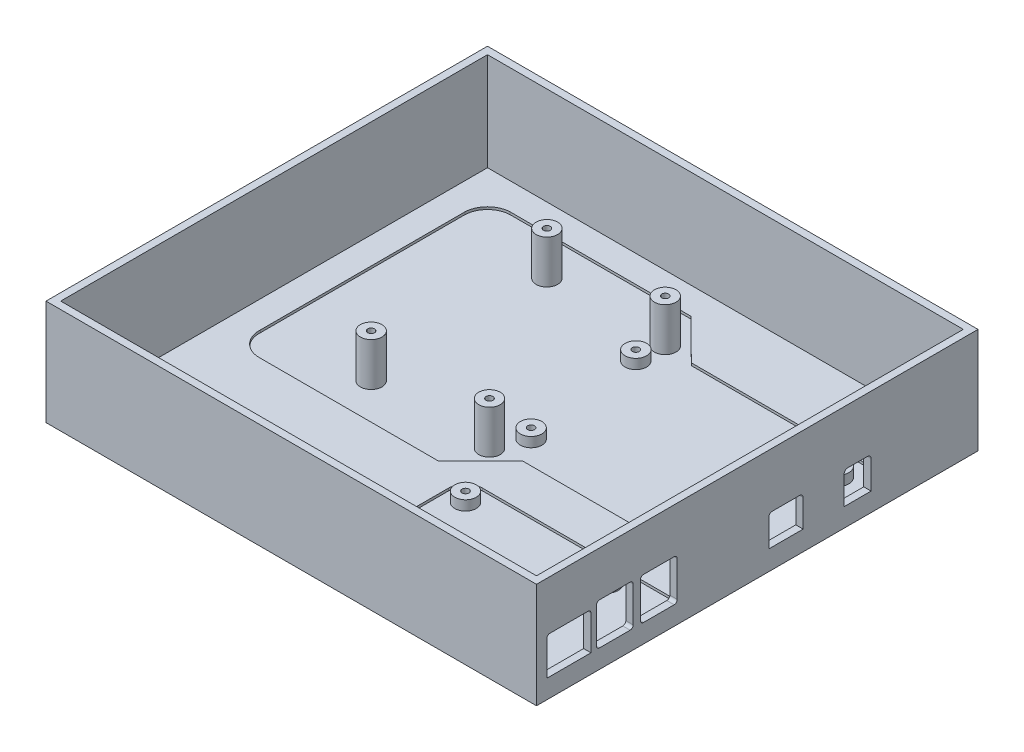
SolidWorks part; units mm, degrees
note: The reader was unsure of these and kept them because the rebuilt part matched: shared geometry of "Sketch1<3>", "Sketch2<2>".
ref_plane "Plano frontal" through (0, 0, 0) normal (0, 0, 1) x (1, 0, 0)
ref_plane "Plano superior" through (0, 0, 0) normal (0, 1, 0) x (1, 0, 0)
ref_plane "Plano direito" through (0, 0, 0) normal (1, 0, 0) x (0, 0, -1)
sketch "Sketch1" plane through (0, -4, 0) normal (0, -1, 0) x (-1, 0, 0)
  line L0 (51.7633, 46.5833) -> (124.0171, 46.5833) construction
  line L1 (144.325, -112.8) -> (-50.075, -112.8)
  line L2 (144.325, -112.8) -> (144.325, 61.5833)
  line L3 (144.325, 61.5833) -> (-50.075, 61.5833)
  line L4 (-50.075, -112.8) -> (-50.075, 61.5833)
  line L5 (-22.175, -112.8) -> (-47.075, -112.8) construction
  line L6 (-50.075, -26.8) -> (-50.075, 26.8) construction
  line L7 (129.325, 41.2631) -> (129.325, -42.2907) construction
  line L8 (-53.075, -115.8) -> (-53.075, 64.5833)
  line L9 (147.325, 64.5833) -> (-53.075, 64.5833)
  line L10 (147.325, -115.8) -> (147.325, 64.5833)
  line L11 (147.325, -115.8) -> (-53.075, -115.8)
  dimension "D1" = 15
  dimension "D2" = 0
  dimension "D3" = 0
  dimension "D4" = 15
  dimension "D5" = 3
extrude "Boss-Extrude1" add sketch "Sketch1" along normal blind 3 contours L4 L1 L2 L3 | L11 L10 L9 L8 L1 L4 L3 L2
extrude "Boss-Extrude2" add sketch "Sketch1<3>" against normal blind 40
sketch "Sketch1<3>" plane through (0, -4, 0) normal (0, -1, 0) x (-1, 0, 0) same geometry as "Sketch1"
sketch "Sketch2" plane through (0, -4, 0) normal (0, 1, 0) x (1, 0, 0)
  circle A0 centre (-94.0836, 35.5996) radius 1.4
  circle A1 centre (-45.9775, 35.8437) radius 1.4
  circle A2 centre (-46.675, 24.55) radius 1.4
  circle A4 centre (34.775, -24.5) radius 1.4
  circle A5 centre (-40.425, -24.5) radius 1.4
  circle A6 centre (-45.6112, -36.3154) radius 1.4
  circle A7 centre (-93.7174, -36.5596) radius 1.4
  circle A8 centre (-31.425, -60.3) radius 1.4
  circle A9 centre (26.575, -60.3) radius 1.4
  circle A13 centre (35.975, 24.55) radius 1.4
  circle A14 centre (-31.425, -109.3) radius 1.4
  circle A15 centre (26.575, -109.3) radius 1.4
  circle A16 centre (-94.0836, 35.5996) radius 4.4
  circle A17 centre (-45.9775, 35.8437) radius 4.4
  circle A18 centre (-46.675, 24.55) radius 4.4
  circle A19 centre (35.975, 24.55) radius 4.4
  circle A20 centre (-40.425, -24.5) radius 4.4
  circle A21 centre (-93.7174, -36.5596) radius 4.4
  circle A22 centre (-45.6112, -36.3154) radius 4.4
  circle A23 centre (34.775, -24.5) radius 4.4
  circle A24 centre (-31.425, -60.3) radius 4.4
  circle A25 centre (26.575, -60.3) radius 4.4
  circle A26 centre (-31.425, -109.3) radius 4.4
  circle A27 centre (26.575, -109.3) radius 4.4
  dimension "D1" = 2.8
  dimension "D2" = 2.8
  dimension "D3" = 2.8
  dimension "D4" = 2.8
  dimension "D5" = 2.8
  dimension "D6" = 2.8
  dimension "D7" = 2.8
  dimension "D8" = 2.8
  dimension "D9" = 2.8
  dimension "D10" = 2.8
  dimension "D11" = 2.8
  dimension "D12" = 2.8
  dimension "D13" = 3
  dimension "D14" = 3
  dimension "D15" = 3
  dimension "D16" = 3
  dimension "D17" = 3
  dimension "D18" = 3
  dimension "D19" = 3
  dimension "D20" = 3
  dimension "D21" = 3
  dimension "D22" = 3
  dimension "D23" = 3
  dimension "D24" = 3
extrude "Boss-Extrude3" add sketch "Sketch2" along normal blind 3
extrude "Boss-Extrude4" add sketch "Sketch2<2>" along normal up to vertex (3 mm away) from surface contours A21 A7 | A22 A6 | A17 A1 | A16 A0
sketch "Sketch2<2>" plane through (0, -4, 0) normal (0, 1, 0) x (1, 0, 0) same geometry as "Sketch2"
sketch "Sketch3" plane through (0, -4, 0) normal (0, 1, 0) x (1, 0, 0)
  line L28 (-123.4721, -52.2167) -> (-50.73, -52.2167)
  line L29 (-50.73, -52.2167) -> (-33.3774, -35.0131)
  line L30 (-33.3774, -35.0131) -> (40.9378, -35.0131)
  line L31 (50.475, -24.618) -> (50.475, 25.373)
  line L32 (40.5344, 34.1869) -> (-33.6785, 34.1869)
  line L33 (-33.6785, 34.1869) -> (-50.1089, 50.5833)
  line L34 (-50.1089, 50.5833) -> (-124.1021, 50.5833)
  line L35 (-133.325, 41.344) -> (-133.325, -42.1846)
  line L36 (-123.4721, -52.2167) -> (-50.73, -52.2167)
  line L37 (-50.73, -52.2167) -> (-33.3774, -35.0131)
  line L38 (-33.3774, -35.0131) -> (40.9378, -35.0131)
  line L39 (50.475, -24.618) -> (50.475, 25.373)
  line L40 (40.5344, 34.1869) -> (-33.6785, 34.1869)
  line L41 (-33.6785, 34.1869) -> (-50.1089, 50.5833)
  line L42 (-50.1089, 50.5833) -> (-124.1021, 50.5833)
  line L43 (-133.325, 41.344) -> (-133.325, -42.1846)
  line L198 (-38.925, -59.8) -> (-38.925, -109.8)
  line L199 (47.075, -52.8) -> (-31.925, -52.8)
  line L200 (-38.925, -59.8) -> (-38.925, -109.8)
  line L201 (47.075, -52.8) -> (-31.925, -52.8)
  line L214 (50.075, 61.5833) -> (-144.325, 61.5833)
  line L215 (50.075, -112.8) -> (50.075, 61.5833)
  line L216 (-144.325, -112.8) -> (50.075, -112.8)
  line L217 (-144.325, 61.5833) -> (-144.325, -112.8)
  line L218 (50.075, 61.5833) -> (-144.325, 61.5833)
  line L219 (50.075, -112.8) -> (50.075, 61.5833)
  line L220 (-144.325, -112.8) -> (50.075, -112.8)
  line L221 (-144.325, 61.5833) -> (-144.325, -112.8)
  arc A12 (-133.325, -42.1846) -> (-123.4721, -52.2167) centre (-123.7475, -42.6326) ccw
  arc A13 (40.9378, -35.0131) -> (50.475, -24.618) centre (40.921, -25.4251) ccw
  arc A14 (50.475, 25.373) -> (40.5344, 34.1869) centre (40.9177, 24.6066) ccw
  arc A15 (-124.1021, 50.5833) -> (-133.325, 41.344) centre (-123.7431, 41.002) ccw
  arc A16 (-133.325, -42.1846) -> (-123.4721, -52.2167) centre (-123.7475, -42.6326) ccw
  arc A17 (40.9378, -35.0131) -> (50.475, -24.618) centre (40.921, -25.4251) ccw
  arc A18 (50.475, 25.373) -> (40.5344, 34.1869) centre (40.9177, 24.6066) ccw
  arc A19 (-124.1021, 50.5833) -> (-133.325, 41.344) centre (-123.7431, 41.002) ccw
  arc A66 (-38.925, -109.8) -> (-31.925, -116.8) centre (-31.925, -109.8) ccw
  arc A67 (53.9771, -58.6333) -> (47.075, -52.8) centre (47.075, -59.8) ccw
  arc A68 (-31.925, -52.8) -> (-38.925, -59.8) centre (-31.925, -59.8) ccw
  arc A69 (-38.925, -109.8) -> (-31.925, -116.8) centre (-31.925, -109.8) ccw
  arc A70 (53.9771, -58.6333) -> (47.075, -52.8) centre (47.075, -59.8) ccw
  arc A71 (-31.925, -52.8) -> (-38.925, -59.8) centre (-31.925, -59.8) ccw
  arc M22 (23.9085, -112.8) -> (29.2415, -112.8) centre (26.575, -109.3) cw
  line M23 (29.2415, -112.8) -> (50.075, -112.8)
  line M24 (50.075, -112.8) -> (50.075, 61.5833)
  arc M28 (-34.0915, -112.8) -> (-28.7585, -112.8) centre (-31.425, -109.3) cw
  line M29 (-28.7585, -112.8) -> (23.9085, -112.8)
  circle M30 centre (26.575, -60.3) radius 4.4
  circle M31 centre (-31.425, -60.3) radius 4.4
  circle M32 centre (34.775, -24.5) radius 4.4
  circle M33 centre (-45.6112, -36.3154) radius 4.4
  circle M34 centre (-93.7174, -36.5596) radius 4.4
  circle M35 centre (-40.425, -24.5) radius 4.4
  circle M36 centre (35.975, 24.55) radius 4.4
  circle M37 centre (-46.675, 24.55) radius 4.4
  circle M38 centre (-45.9775, 35.8437) radius 4.4
  circle M39 centre (-94.0836, 35.5996) radius 4.4
  dimension "D1" = 4
  dimension "D2" = 4
  dimension "D3" = 0
extrude "Cut-Extrude1" cut sketch "Sketch3" against normal blind 1 contours L42 A19 L43 A16 L36 L37 L38 A17 L219 A18 L40 L41 M33 M35 M37 M39 M38 M36 M34 M32 | L201 A71 L200 A69 L220 A70 M28 M29 M22 M23 M24 M30 M31
sketch "Sketch4" plane through (53.075, 0, 0) normal (1, 0, 0) x (0, 0, -1)
  line L17 (9.9, 0.63) -> (20.9, 0.63)
  line L18 (20.9, 0.63) -> (20.9, 12.13)
  line L19 (9.9, 12.13) -> (9.9, 0.63)
  line L20 (19.4, 13.63) -> (11.4, 13.63)
  line L21 (9.9, 0.63) -> (20.9, 0.63)
  line L22 (20.9, 0.63) -> (20.9, 12.13)
  line L23 (9.9, 12.13) -> (9.9, 0.63)
  line L24 (19.4, 13.63) -> (11.4, 13.63)
  line L42 (-8.32, 13.68) -> (-19.44, 13.68)
  line L43 (-8.32, 13.68) -> (-19.44, 13.68)
  line L61 (-20.9, 12.22) -> (-20.9, 12.12)
  line L62 (-6.86, 12.22) -> (-6.86, 12.12)
  line L66 (-6.86, 1.06) -> (-6.86, 2.47)
  line L67 (-6.86, 2.47) -> (-6.86, 12.12)
  line L68 (-20.9, 1.06) -> (-6.86, 1.06)
  line L69 (-20.9, 2.47) -> (-20.9, 1.06)
  line L70 (-20.9, 12.12) -> (-20.9, 2.47)
  line L71 (-6.86, 1.06) -> (-6.86, 2.47)
  line L72 (-6.86, 2.47) -> (-6.86, 12.12)
  line L73 (-20.9, 1.06) -> (-6.86, 1.06)
  line L74 (-20.9, 2.47) -> (-20.9, 1.06)
  line L75 (-20.9, 12.12) -> (-20.9, 2.47)
  line L208 (-71.3, 17.63) -> (-60.3, 17.63)
  line L209 (-72.05, 17.63) -> (-71.3, 17.63)
  line L210 (-71.3, 17.63) -> (-60.3, 17.63)
  line L211 (-72.05, 17.63) -> (-71.3, 17.63)
  line L213 (-90.05, 0.63) -> (-89.3, 0.63)
  line L214 (-91.3, 3.13) -> (-91.3, 1.88)
  line L215 (-89.3, 0.63) -> (-78.3, 0.63)
  line L216 (-78.3, 0.63) -> (-77.55, 0.63)
  line L217 (-76.3, 1.88) -> (-76.3, 3.13)
  line L218 (-91.3, 15.13) -> (-91.3, 3.13)
  line L219 (-76.3, 3.13) -> (-76.3, 15.13)
  line L220 (-76.3, 15.13) -> (-76.3, 16.38)
  line L221 (-77.55, 17.63) -> (-78.3, 17.63)
  line L222 (-91.3, 16.38) -> (-91.3, 15.13)
  line L223 (-78.3, 17.63) -> (-89.3, 17.63)
  line L224 (-89.3, 17.63) -> (-90.05, 17.63)
  line L225 (-90.05, 0.63) -> (-89.3, 0.63)
  line L226 (-91.3, 3.13) -> (-91.3, 1.88)
  line L227 (-89.3, 0.63) -> (-78.3, 0.63)
  line L228 (-78.3, 0.63) -> (-77.55, 0.63)
  line L229 (-76.3, 1.88) -> (-76.3, 3.13)
  line L230 (-91.3, 15.13) -> (-91.3, 3.13)
  line L231 (-76.3, 3.13) -> (-76.3, 15.13)
  line L232 (-76.3, 15.13) -> (-76.3, 16.38)
  line L233 (-77.55, 17.63) -> (-78.3, 17.63)
  line L234 (-91.3, 16.38) -> (-91.3, 15.13)
  line L235 (-78.3, 17.63) -> (-89.3, 17.63)
  line L236 (-89.3, 17.63) -> (-90.05, 17.63)
  line L335 (-59.55, 17.63) -> (-60.3, 17.63)
  line L336 (-58.3, 15.13) -> (-58.3, 16.38)
  line L337 (-58.3, 3.13) -> (-58.3, 15.13)
  line L338 (-58.3, 1.88) -> (-58.3, 3.13)
  line L339 (-60.3, 0.63) -> (-59.55, 0.63)
  line L340 (-71.3, 0.63) -> (-60.3, 0.63)
  line L341 (-72.05, 0.63) -> (-71.3, 0.63)
  line L342 (-73.3, 3.13) -> (-73.3, 1.88)
  line L343 (-73.3, 15.13) -> (-73.3, 3.13)
  line L344 (-73.3, 16.38) -> (-73.3, 15.13)
  line L345 (-59.55, 17.63) -> (-60.3, 17.63)
  line L346 (-58.3, 15.13) -> (-58.3, 16.38)
  line L347 (-58.3, 3.13) -> (-58.3, 15.13)
  line L348 (-58.3, 1.88) -> (-58.3, 3.13)
  line L349 (-60.3, 0.63) -> (-59.55, 0.63)
  line L350 (-71.3, 0.63) -> (-60.3, 0.63)
  line L351 (-72.05, 0.63) -> (-71.3, 0.63)
  line L352 (-73.3, 3.13) -> (-73.3, 1.88)
  line L353 (-73.3, 15.13) -> (-73.3, 3.13)
  line L354 (-73.3, 16.38) -> (-73.3, 15.13)
  line L357 (-93.55, 14.73) -> (-93.55, 1.63)
  line L358 (-111.55, 1.63) -> (-111.55, 14.73)
  line L359 (-110.35, 15.93) -> (-94.75, 15.93)
  line L360 (-93.55, 14.73) -> (-93.55, 1.63)
  line L361 (-111.55, 1.63) -> (-111.55, 14.73)
  line L362 (-110.35, 15.93) -> (-94.75, 15.93)
  line L371 (-111.55, 1.63) -> (-111.55, 0.63)
  line L372 (-104.55, 0.63) -> (-100.55, 0.63)
  line L373 (-104.55, 0.63) -> (-100.55, 0.63)
  line L374 (-111.55, 0.63) -> (-104.55, 0.63)
  line L375 (-100.55, 0.63) -> (-93.55, 0.63)
  line L376 (-93.55, 0.63) -> (-93.55, 1.63)
  arc A10 (20.9, 12.13) -> (19.4, 13.63) centre (19.4, 12.13) ccw
  arc A11 (11.4, 13.63) -> (9.9, 12.13) centre (11.4, 12.13) ccw
  arc A12 (20.9, 12.13) -> (19.4, 13.63) centre (19.4, 12.13) ccw
  arc A13 (11.4, 13.63) -> (9.9, 12.13) centre (11.4, 12.13) ccw
  arc A28 (-19.44, 13.68) -> (-20.9, 12.22) centre (-19.44, 12.22) ccw
  arc A29 (-6.86, 12.22) -> (-8.32, 13.68) centre (-8.32, 12.22) ccw
  arc A30 (-19.44, 13.68) -> (-20.9, 12.22) centre (-19.44, 12.22) ccw
  arc A31 (-6.86, 12.22) -> (-8.32, 13.68) centre (-8.32, 12.22) ccw
  arc A114 (-72.05, 17.63) -> (-73.05, 17.13) centre (-72.05, 16.38) ccw
  arc A115 (-72.05, 17.63) -> (-73.05, 17.13) centre (-72.05, 16.38) ccw
  arc A120 (-91.05, 1.13) -> (-90.05, 0.63) centre (-90.05, 1.88) ccw
  arc A121 (-91.3, 1.88) -> (-91.05, 1.13) centre (-90.05, 1.88) ccw
  arc A122 (-77.55, 0.63) -> (-76.55, 1.13) centre (-77.55, 1.88) ccw
  arc A123 (-76.55, 1.13) -> (-76.3, 1.88) centre (-77.55, 1.88) ccw
  arc A124 (-76.3, 16.38) -> (-76.55, 17.13) centre (-77.55, 16.38) ccw
  arc A125 (-76.55, 17.13) -> (-77.55, 17.63) centre (-77.55, 16.38) ccw
  arc A126 (-91.05, 17.13) -> (-91.3, 16.38) centre (-90.05, 16.38) ccw
  arc A127 (-90.05, 17.63) -> (-91.05, 17.13) centre (-90.05, 16.38) ccw
  arc A128 (-91.05, 1.13) -> (-90.05, 0.63) centre (-90.05, 1.88) ccw
  arc A129 (-91.3, 1.88) -> (-91.05, 1.13) centre (-90.05, 1.88) ccw
  arc A130 (-77.55, 0.63) -> (-76.55, 1.13) centre (-77.55, 1.88) ccw
  arc A131 (-76.55, 1.13) -> (-76.3, 1.88) centre (-77.55, 1.88) ccw
  arc A132 (-76.3, 16.38) -> (-76.55, 17.13) centre (-77.55, 16.38) ccw
  arc A133 (-76.55, 17.13) -> (-77.55, 17.63) centre (-77.55, 16.38) ccw
  arc A134 (-91.05, 17.13) -> (-91.3, 16.38) centre (-90.05, 16.38) ccw
  arc A135 (-90.05, 17.63) -> (-91.05, 17.13) centre (-90.05, 16.38) ccw
  arc A200 (-58.55, 17.13) -> (-59.55, 17.63) centre (-59.55, 16.38) ccw
  arc A201 (-58.3, 16.38) -> (-58.55, 17.13) centre (-59.55, 16.38) ccw
  arc A202 (-58.55, 1.13) -> (-58.3, 1.88) centre (-59.55, 1.88) ccw
  arc A203 (-59.55, 0.63) -> (-58.55, 1.13) centre (-59.55, 1.88) ccw
  arc A204 (-73.05, 1.13) -> (-72.05, 0.63) centre (-72.05, 1.88) ccw
  arc A205 (-73.3, 1.88) -> (-73.05, 1.13) centre (-72.05, 1.88) ccw
  arc A206 (-73.05, 17.13) -> (-73.3, 16.38) centre (-72.05, 16.38) ccw
  arc A207 (-58.55, 17.13) -> (-59.55, 17.63) centre (-59.55, 16.38) ccw
  arc A208 (-58.3, 16.38) -> (-58.55, 17.13) centre (-59.55, 16.38) ccw
  arc A209 (-58.55, 1.13) -> (-58.3, 1.88) centre (-59.55, 1.88) ccw
  arc A210 (-59.55, 0.63) -> (-58.55, 1.13) centre (-59.55, 1.88) ccw
  arc A211 (-73.05, 1.13) -> (-72.05, 0.63) centre (-72.05, 1.88) ccw
  arc A212 (-73.3, 1.88) -> (-73.05, 1.13) centre (-72.05, 1.88) ccw
  arc A213 (-73.05, 17.13) -> (-73.3, 16.38) centre (-72.05, 16.38) ccw
  arc A215 (-93.55, 14.73) -> (-94.75, 15.93) centre (-94.75, 14.73) ccw
  arc A216 (-110.35, 15.93) -> (-111.55, 14.73) centre (-110.35, 14.73) ccw
  arc A217 (-93.55, 14.73) -> (-94.75, 15.93) centre (-94.75, 14.73) ccw
  arc A218 (-110.35, 15.93) -> (-111.55, 14.73) centre (-110.35, 14.73) ccw
  dimension "D1" = 1
  dimension "D2" = 1
  dimension "D3" = 1
  dimension "D4" = 1
  dimension "D5" = 1
  dimension "D6" = 1
  dimension "D7" = 1
  dimension "D8" = 1
extrude "Cut-Extrude2" cut sketch "Sketch4" against normal blind 5
sketch "Sketch5" plane through (0, 0, 115.8) normal (0, 0, 1) x (1, 0, 0)
  line L0 (-10.0854, 3.1084) -> (-10.125, 3.1084)
  line L71 (13.975, 1.63) -> (13.975, 0.63)
  line L72 (13.975, 0.63) -> (23.175, 0.63)
  line L73 (23.175, 0.63) -> (23.175, 1.63)
  line L75 (22.175, 1.63) -> (47.075, 1.63) construction
  line L78 (23.175, 7.73) -> (23.175, 1.63)
  line L79 (13.975, 1.63) -> (13.975, 7.73)
  line L80 (15.075, 8.83) -> (16.575, 8.83)
  line L81 (16.575, 8.83) -> (17.075, 8.83)
  line L82 (17.075, 8.83) -> (20.075, 8.83)
  line L83 (20.075, 8.83) -> (20.575, 8.83)
  line L84 (20.575, 8.83) -> (22.075, 8.83)
  line L85 (23.175, 7.73) -> (23.175, 1.63)
  line L86 (13.975, 1.63) -> (13.975, 7.73)
  line L87 (15.075, 8.83) -> (16.575, 8.83)
  line L88 (16.575, 8.83) -> (17.075, 8.83)
  line L89 (17.075, 8.83) -> (20.075, 8.83)
  line L90 (20.075, 8.83) -> (20.575, 8.83)
  line L91 (20.575, 8.83) -> (22.075, 8.83)
  line L153 (-2.925, 9.13) -> (-2.925, 0.23) construction
  line L158 (4.2354, 3.1084) -> (4.275, 3.1084)
  line L159 (5.575, 4.4084) -> (5.575, 7.83)
  line L160 (-11.425, 7.83) -> (-11.425, 4.4084)
  line L161 (4.275, 9.13) -> (-10.125, 9.13)
  line L162 (4.2354, 3.1084) -> (4.275, 3.1084)
  line L163 (5.575, 4.4084) -> (5.575, 7.83)
  line L164 (-11.425, 7.83) -> (-11.425, 4.4084)
  line L165 (4.275, 9.13) -> (-10.125, 9.13)
  arc A0 (-10.125, 3.1084) -> (-11.425, 4.4084) centre (-10.125, 4.4084) cw
  arc A16 (23.175, 7.73) -> (22.075, 8.83) centre (22.075, 7.73) ccw
  arc A17 (15.075, 8.83) -> (13.975, 7.73) centre (15.075, 7.73) ccw
  arc A18 (23.175, 7.73) -> (22.075, 8.83) centre (22.075, 7.73) ccw
  arc A19 (15.075, 8.83) -> (13.975, 7.73) centre (15.075, 7.73) ccw
  arc A80 (4.275, 3.1084) -> (5.575, 4.4084) centre (4.275, 4.4084) ccw
  arc A81 (5.575, 7.83) -> (4.275, 9.13) centre (4.275, 7.83) ccw
  arc A82 (-10.125, 9.13) -> (-11.425, 7.83) centre (-10.125, 7.83) ccw
  arc A83 (4.275, 3.1084) -> (5.575, 4.4084) centre (4.275, 4.4084) ccw
  arc A84 (5.575, 7.83) -> (4.275, 9.13) centre (4.275, 7.83) ccw
  arc A85 (-10.125, 9.13) -> (-11.425, 7.83) centre (-10.125, 7.83) ccw
  dimension "D2" = 1
  dimension "D1" = 1
  dimension "D3" = 1
